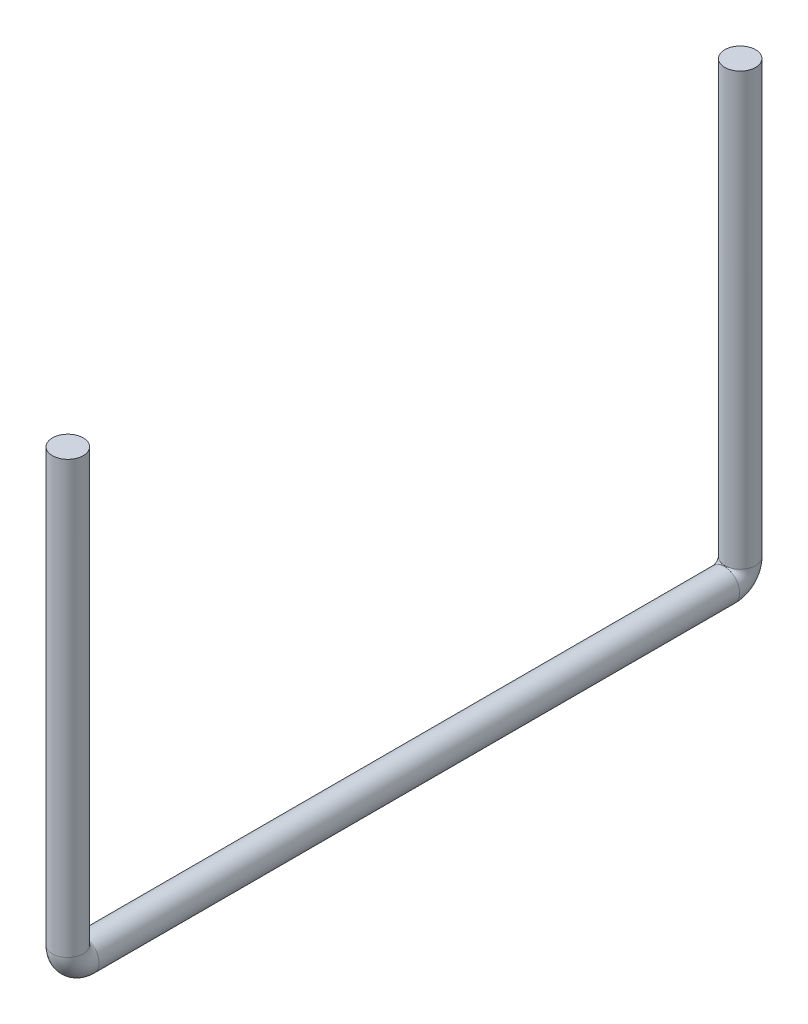
SolidWorks part; units mm, degrees
ref_plane "Front Plane" through (0, 0, 0) normal (0, 0, 1) x (1, 0, 0)
ref_plane "Top Plane" through (0, 0, 0) normal (0, 1, 0) x (1, 0, 0)
ref_plane "Right Plane" through (0, 0, 0) normal (1, 0, 0) x (0, 0, -1)
sketch "Sketch1" plane through (0, 0, 0) normal (0, 0, 1) x (1, 0, 0)
  circle A0 centre (0, 0) radius 12.7
extrude "Boss-Extrude1" add sketch "Sketch1" along normal blind 528.066
sketch "Sketch4" plane through (0, 0, 0) normal (0, 0, -1) x (-1, 0, 0)
  line L0 (-1001.0583, 13.0758) -> (48998.9417, 13.0758) construction
revolve "Revolve20" add sketch "Sketch1<4>" angle 90 about L0 reverse direction yes
sketch "Sketch1<4>" plane through (0, 0, 0) normal (0, 0, 1) x (1, 0, 0) same geometry as "Sketch1"
ref_plane "Center Plane" through (0, 0, 264.033) normal (0, 0, 1) x (1, 0, 0)
sketch "Sketch8" plane through (0, 13.0758, 0) normal (0, 1, 0) x (1, 0, 0)
  circle A0 centre (0, 13.0758) radius 12.7
extrude "Boss-Extrude2" add sketch "Sketch8" along normal blind 355.6
mirror "Mirror2" about plane through (0, 0, 264.033) normal (0, 0, 1) of bodies 104 102
